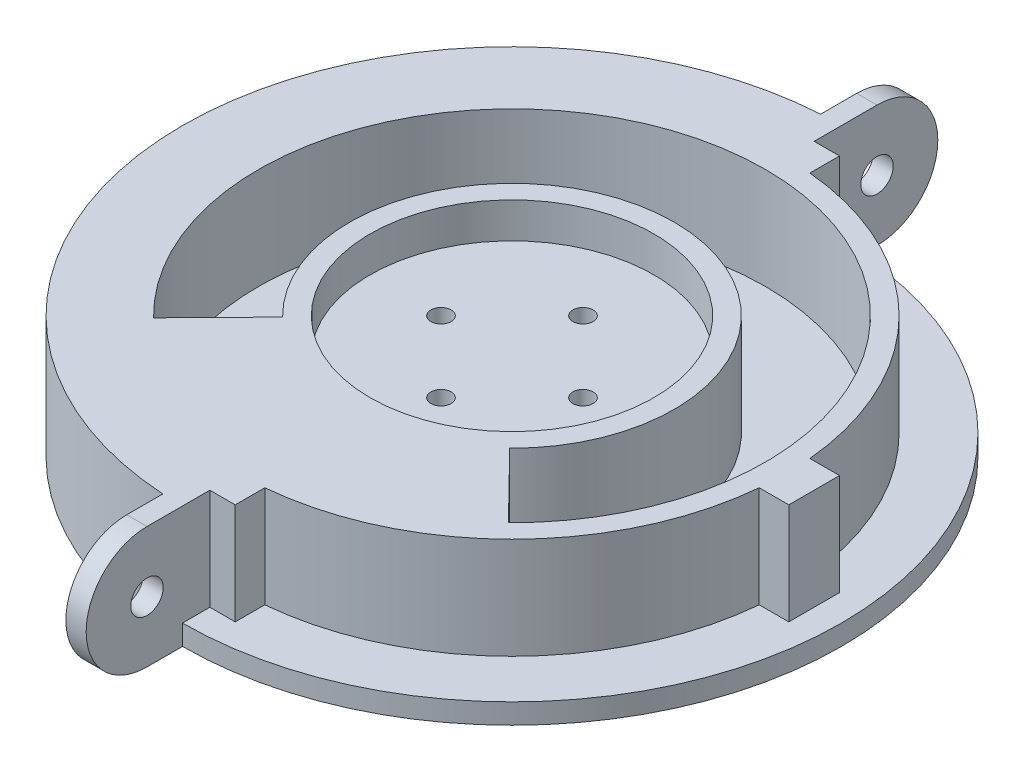
SolidWorks part; units mm, degrees
ref_plane "Front Plane" through (0, 0, 0) normal (0, 0, 1) x (1, 0, 0)
ref_plane "Top Plane" through (0, 0, 0) normal (0, 1, 0) x (1, 0, 0)
ref_plane "Right Plane" through (0, 0, 0) normal (1, 0, 0) x (0, 0, -1)
sketch "Sketch1" plane through (0, 0, 0) normal (0, 1, 0) x (1, 0, 0)
  line L0 (-17.5, -17.8536) -> (-11.2, -11.4263)
  line L1 (0, -55) -> (0, 55) construction
  line L2 (17.5, -17.8536) -> (11.2, -11.4263)
  line L4 (-17.5, -17.8536) -> (3.8221, -38.7535) construction
  circle A0 centre (0, 0) radius 27
  arc A1 (11.2, -11.4263) -> (-11.2, -11.4263) centre (0, 0) ccw
  arc A2 (17.5, -17.8536) -> (-17.5, -17.8536) centre (0, 0) ccw
  circle A3 centre (0, 0) radius 14
  arc A4 (16.5039, 11.7639) -> (14.35, -14.6399) centre (0.1913, -0.1952) cw construction
  circle A5 centre (0, 0) radius 19.9533 construction
  dimension "D1" = 54
  dimension "D2" = 2
  dimension "D3" = 9
  dimension "D4" = 2
  dimension "D5" = 35
extrude "Boss-Extrude1" add sketch "Sketch1" along normal blind 10
sketch "Sketch2" plane through (0, 0, 0) normal (0, -1, 0) x (1, 0, 0)
  circle A0 centre (0, 0) radius 32.5
  circle A1 centre (0, 0) radius 14 construction
  circle A2 centre (0, 0) radius 14 construction
  dimension "D1" = 65
extrude "Boss-Extrude2" add sketch "Sketch2" along normal blind 2
sketch "Sketch3" plane through (0, 0, 0) normal (0, 1, 0) x (1, 0, 0)
  line L0 (0, -5.5) -> (0, 5.5) construction
  line L1 (-2.5, 29.8) -> (2.5, 29.8)
  line L2 (-2.5, 29.8) -> (-2.5, 25.4032)
  line L3 (-2.5, 25.4032) -> (2.5, 25.4032)
  line L4 (2.5, 29.8) -> (2.5, 25.4032)
  line L5 (-2.5, 29.8) -> (2.5, 25.4032) construction
  line L6 (-2.5, 25.4032) -> (2.5, 29.8) construction
  line L7 (29.8, 2.5) -> (25.4032, 2.5)
  line L8 (29.8, 2.5) -> (29.8, -2.5)
  line L9 (29.8, -2.5) -> (25.4032, -2.5)
  line L10 (25.4032, 2.5) -> (25.4032, -2.5)
  line L11 (2.5, -29.8) -> (2.5, -25.4032)
  line L12 (2.5, -29.8) -> (-2.5, -29.8)
  line L13 (-2.5, -29.8) -> (-2.5, -25.4032)
  line L14 (2.5, -25.4032) -> (-2.5, -25.4032)
  line L15 (-29.8, -2.5) -> (-25.4032, -2.5)
  line L16 (-29.8, -2.5) -> (-29.8, 2.5)
  line L17 (-29.8, 2.5) -> (-25.4032, 2.5)
  line L18 (-25.4032, -2.5) -> (-25.4032, 2.5)
  circle A1 centre (0, 0) radius 27 construction
  point P0 (0, 27.6016)
  dimension "D2" = 29.8
  dimension "D1" = 5
  dimension "D3" = 4
extrude "Boss-Extrude3" add sketch "Sketch3" along normal blind 10
sketch "Sketch5" plane through (0, 0, 0) normal (0, 1, 0) x (1, 0, 0)
  line L0 (0, 29.8) -> (0, 32.5)
  line L1 (2.5, 29.8) -> (-2.5, 29.8) construction
  line L2 (0, -6.6) -> (0, 6.6) construction
  line L3 (0, -29.8) -> (0, -32.5)
  line L4 (0, 29.8) -> (-2.5, 29.8)
  line L5 (-2.5, 29.8) -> (-2.5, 26.884)
  line L6 (-26.884, 2.5) -> (-29.8, 2.5)
  line L7 (-29.8, 2.5) -> (-29.8, -2.5)
  line L8 (-29.8, -2.5) -> (-26.884, -2.5)
  line L9 (-2.5, -26.884) -> (-2.5, -29.8)
  line L10 (-2.5, -29.8) -> (0, -29.8)
  line L11 (-2.5, -29.8) -> (2.5, -29.8) construction
  circle A0 centre (0, 0) radius 32.5 construction
  arc A1 (0, 32.5) -> (0, -32.5) centre (0, 0) ccw
  arc A2 (-26.884, 2.5) -> (-2.5, 26.884) centre (0, 0) cw
  arc A3 (-26.884, -2.5) -> (-2.5, -26.884) centre (0, 0) ccw
extrude "Boss-Extrude4" add sketch "Sketch5" along normal up to surface (10 mm away) up to face at (0, 10, 0)
ref_plane "Plane1" through (0, 6.5, 0) normal (0, 1, 0) x (1, 0, 0)
sketch "Sketch6" plane through (0, 6.5, 0) normal (0, 1, 0) x (1, 0, 0)
  circle A0 centre (0, 0) radius 14
extrude "Boss-Extrude5" add sketch "Sketch6" against normal up to surface (6.5 mm away) up to face at (0, 0, 14)
sketch "Sketch4" plane through (0, -2, 0) normal (0, -1, 0) x (1, 0, 0)
  circle A0 centre (0, 0) radius 7 construction
  circle A1 centre (0, -7) radius 1
  circle A2 centre (-7, 0) radius 1
  circle A3 centre (0, 7) radius 1
  circle A4 centre (7, 0) radius 1
  point P14 (0, 0)
  dimension "D1" = 14
  dimension "D2" = 2
  dimension "D3" = 4
extrude "Cut-Extrude1" cut sketch "Sketch4" against normal through all both and the other way through all
sketch "Sketch7" plane through (0, 10, 0) normal (0, 1, 0) x (1, 0, 0)
  line L0 (11.2, -11.4263) -> (17.5, -17.8536) construction
  circle A0 centre (0, 0) radius 20.5 construction
  circle A1 centre (0, -20.5) radius 1.6
  point P5 (14.35, -14.6399)
  dimension "D1" = 3.2
extrude "Cut-Extrude2" [suppressed] cut sketch "Sketch7" against normal through all both and the other way through all
sketch "Sketch8" [suppressed] plane through (0, -2, 0) normal (0, -1, 0) x (1, 0, 0)
  line L0 (6.6, 0) -> (-6.6, 0) construction
  line L1 (-3.1177, 20.5) -> (-1.5588, 17.8)
  line L2 (-1.5588, 17.8) -> (1.5588, 17.8)
  line L3 (1.5588, 17.8) -> (3.1177, 20.5)
  line L4 (3.1177, 20.5) -> (1.5588, 23.2)
  line L5 (1.5588, 23.2) -> (-1.5588, 23.2)
  line L6 (-1.5588, 23.2) -> (-3.1177, 20.5)
  circle A0 centre (0, 20.5) radius 2.7 construction
  dimension "D1" = 5.4
extrude "Cut-Extrude3" [suppressed] cut sketch "Sketch8" against normal blind 4
sketch "Sketch9" plane through (0, 0, 0) normal (1, 0, 0) x (0, 0, -1)
  line L0 (32.5, 10) -> (-32.5, 10) construction
  line L1 (36, -2) -> (30.5, -2)
  line L3 (36, 10) -> (30.5, 10)
  line L4 (30.5, -2) -> (30.5, 10)
  line L5 (32.5, 10) -> (32.5, 0) construction
  arc A0 (36, -2) -> (36, 10) centre (36, 4) ccw
  circle A1 centre (36, 4) radius 1.6
  circle A2 centre (36, 4) radius 3 construction
  dimension "D4" = 3.2
  dimension "D5" = 6
  dimension "D1" = 3.5
  dimension "D2" = 2
  dimension "D3" = 12
extrude "Boss-Extrude6" add sketch "Sketch9" against normal blind 2
mirror "Mirror1" about plane through (0, 0, 0) normal (0, 0, 1) of "Boss-Extrude6"
